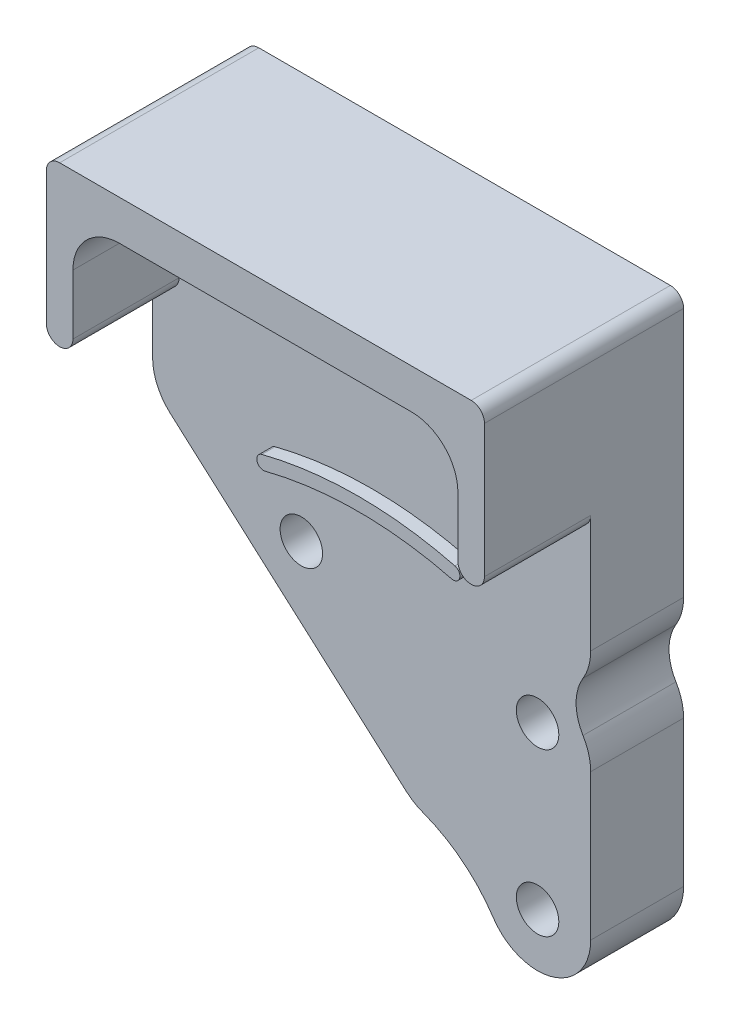
SolidWorks part; units mm, degrees
material "6061-T6 (SS)"
ref_plane "Front Plane" through (0, 0, 0) normal (0, 0, 1) x (1, 0, 0)
ref_plane "Top Plane" through (0, 0, 0) normal (0, 1, 0) x (1, 0, 0)
ref_plane "Right Plane" through (0, 0, 0) normal (1, 0, 0) x (0, 0, -1)
sketch "Sketch1" plane through (0, 0, 0) normal (0, 0, 1) x (1, 0, 0)
  line L0 (-16.5, 28) -> (6.6353, 7.4815)
  line L1 (-6.6353, 7.4815) -> (16.5, 28)
  line L2 (-16.5, 28) -> (-16.5, 47)
  line L3 (-16.5, 47) -> (16.5, 47)
  line L4 (16.5, 47) -> (16.5, 28)
  line L5 (6.6353, 7.4815) -> (16.5, -1.2674)
  line L6 (16.5, -1.2674) -> (16.5, 28)
  circle A0 centre (0, 0) radius 11
  circle A1 centre (0, 0) radius 32.5
  circle A2 centre (0, 0) radius 10
  dimension "D1" = 22
  dimension "D2" = 65
  dimension "D5" = 20
  dimension "D3" = 33
  dimension "D4" = 47
extrude "Boss-Extrude1" add sketch "Sketch1" along normal blind 7 contours A0 L5 L6 L1 | L1 A1 L0 A0 | A1 L4 L3 L2
sketch "Sketch2" plane through (0, 0, 7) normal (0, 0, 1) x (1, 0, 0)
  line L0 (-16.5, 35) -> (-16.5, 47)
  line L2 (-16.5, 47) -> (16.5, 47)
  line L3 (16.5, 47) -> (16.5, 35)
  line L5 (16.5, 35) -> (14.5, 35)
  line L6 (14.5, 35) -> (14.5, 44)
  line L7 (14.5, 44) -> (-14.5, 44)
  line L8 (-14.5, 44) -> (-14.5, 35)
  line L9 (-14.5, 35) -> (-16.5, 35)
  line L11 (16.5, 47) -> (16.5, -1.2674) construction
  line L12 (-16.5, 28) -> (-16.5, 47) construction
  line L14 (-16.5, 47) -> (16.5, 47) construction
  dimension "D1" = 3
  dimension "D2" = 2
  dimension "D3" = 2
  dimension "D4" = 12
extrude "Boss-Extrude2" add sketch "Sketch2" along normal blind 8
fillet "Fillet1" radius 3.5 2 edges at (14.5, 44, 11) (-14.5, 44, 11)
sketch "Sketch3" plane through (0, 0, 0) normal (0, 0, -1) x (-1, 0, 0)
  circle A0 centre (-19, 23.2164) radius 3.6
  circle A1 centre (19, 23.2164) radius 3.55
  dimension "D1" = 7.2
  dimension "D2" = 7.1
sketch "Sketch4" plane through (0, 0, 7) normal (0, 0, 1) x (1, 0, 0)
  line L0 (-7.7632, 28.4602) -> (-7.5, 27.4955)
  line L1 (7.5, 27.4955) -> (7.7632, 28.4602)
  circle A0 centre (0, 0) radius 28.5
  circle A1 centre (0, 0) radius 29.5
  dimension "D1" = 57
  dimension "D2" = 1
  dimension "D3" = 15
extrude "Boss-Extrude3" add sketch "Sketch4" along normal blind 1 contours L1 A1 L0 A0
fillet "Fillet5" radius 0.5 4 edges at (7.7632, 28.4602, 7.5) (7.5, 27.4955, 7.5) (-7.7632, 28.4602, 7.5) (-7.5, 27.4955, 7.5)
extrude "Cut-Extrude2" cut sketch "Sketch3" against normal blind 12
fillet "Fillet7" radius 4 4 edges at (3.2068, 10.5222, 3.5) (16.5, -1.2674, 3.5) (16.5, 20.626, 3.5) (-16.5, 28, 3.5)
fillet "Fillet8" radius 1 10 edges at (-16.5, 47, 7.5) (16.5, 47, 7.5) (-14.5, 35, 11) (14.5, 35, 11) (-15.5, 35, 15) (15.5, 35, 15)
sketch "Sketch5" plane through (0, 0, 7) normal (0, 0, 1) x (1, 0, 0)
  line L0 (-15.1541, 26.8063) -> (2.6064, 11.0547) construction
  line L1 (16.5, 7.6133) -> (16.5, 19.2781) construction
  circle A0 centre (-11, 40.5) radius 1.65
  circle A1 centre (11, 40.5) radius 1.65
  circle A2 centre (12.5, 8.2916) radius 1.6
  arc A3 (-5.2947, 23.4087) -> (12.5, 20.4878) centre (0, 0) cw
  circle A4 centre (-5.2947, 23.4087) radius 1.6
  circle A5 centre (12.5, 20.4878) radius 1.6
  dimension "D1" = 3.3
  dimension "D2" = 3.3
  dimension "D3" = 3.2
  dimension "D4" = 3.2
  dimension "D5" = 3.2
  dimension "D6" = 24
  dimension "D7" = 4
  dimension "D8" = 4
extrude "Cut-Extrude3" cut sketch "Sketch5" against normal through all
fillet "Fillet12" radius 4 1 edges at (10.0637, 4.4408, 3.5)
